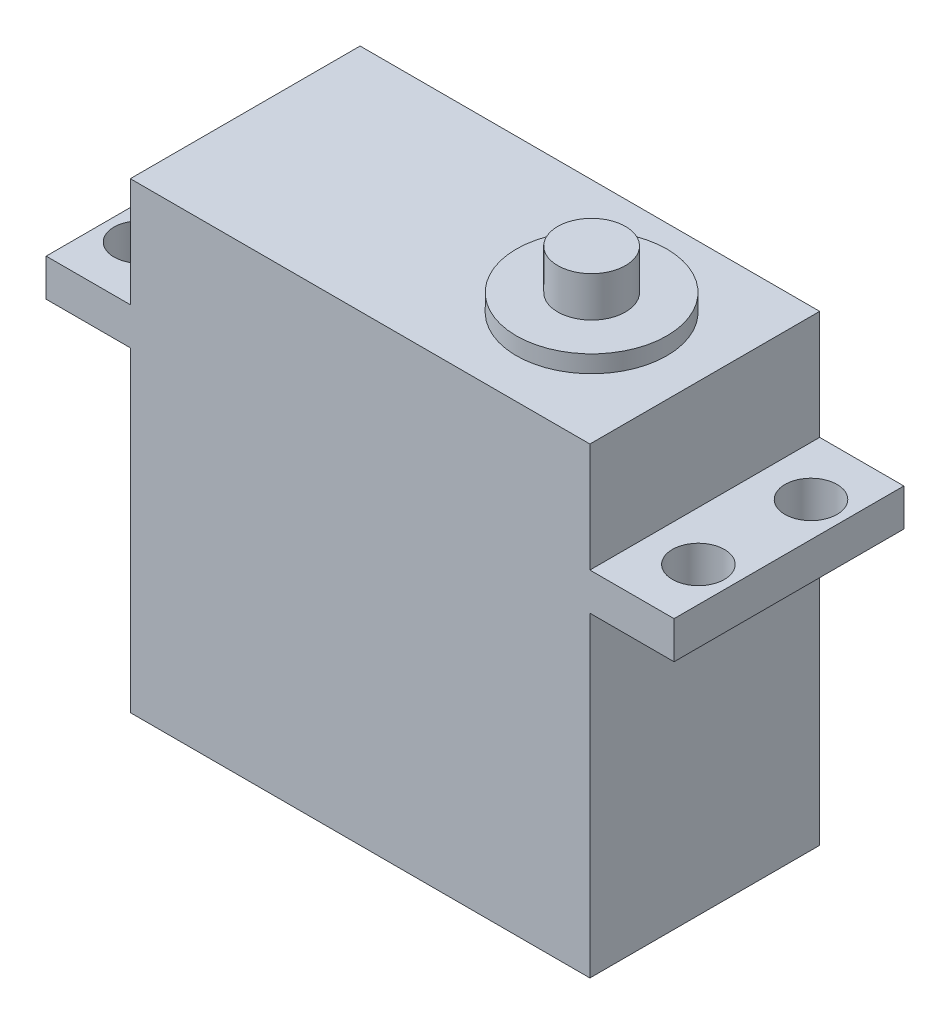
SolidWorks part; units mm, degrees
ref_plane "Front" through (0, 0, 0) normal (0, 0, 1) x (1, 0, 0)
ref_plane "Top" through (0, 0, 0) normal (0, 1, 0) x (1, 0, 0)
ref_plane "Right" through (0, 0, 0) normal (1, 0, 0) x (0, 0, -1)
sketch "Sketch1" plane through (0, 0, 0) normal (0, 0, 1) x (1, 0, 0)
  line L0 (0, 0) -> (40, 0)
  line L1 (40, 0) -> (40, 27.5)
  line L2 (40, 27.5) -> (47.325, 27.5)
  line L3 (47.325, 27.5) -> (47.325, 30.75)
  line L4 (47.325, 30.75) -> (40, 30.75)
  line L5 (40, 30.75) -> (40, 40.25)
  line L6 (40, 40.25) -> (0, 40.25)
  line L7 (0, 40.25) -> (0, 30.75)
  line L8 (0, 30.75) -> (-7.325, 30.75)
  line L9 (-7.325, 30.75) -> (-7.325, 27.5)
  line L10 (-7.325, 27.5) -> (0, 27.5)
  line L11 (0, 27.5) -> (0, 0)
  dimension "D1" = 27.5
  dimension "D2" = 40
  dimension "D3" = 9.5
  dimension "D4" = 54.65
  dimension "D5" = 3.25
extrude "Boss-Extrude1" add sketch "Sketch1" along normal blind 20
sketch "Sketch2" plane through (0, 30.75, 0) normal (0, 1, 0) x (1, 0, 0)
  line L0 (-4.3, -5.0554) -> (20, -5.0554) construction
  line L1 (20, -5.0554) -> (44.3, -5.0554) construction
  line L2 (20, 0) -> (20, -5.0554) construction
  line L3 (40, 0) -> (0, 0) construction
  circle A0 centre (-4.3, -5.0554) radius 2.2648
  circle A1 centre (-4.3, -14.8554) radius 2.2648
  circle A2 centre (44.3, -14.8554) radius 2.2648
  circle A3 centre (44.3, -5.0554) radius 2.2648
  dimension "D1" = 48.6
  dimension "D2" = 9.8
extrude "Cut-Extrude1" cut sketch "Sketch2" against normal up to surface (3.25 mm away) up to face at (-3.6625, 27.5, 10)
sketch "Sketch3" plane through (0, 40.25, 0) normal (0, 1, 0) x (1, 0, 0)
  circle A0 centre (30.15, -10) radius 2.95
  arc A1 (-2.0352, -14.8554) -> (-4.3, -17.1203) centre (-4.3, -14.8554) ccw
  circle A2 centre (-4.3, -14.8554) radius 2.2648 construction
  dimension "D2" = 5.9
  dimension "D1" = 34.45
extrude "Boss-Extrude2" add sketch "Sketch3" along normal blind 5 contours A0 region at (30.15, 40.25, 10)
sketch "Sketch4" plane through (0, 40.25, 0) normal (0, 1, 0) x (1, 0, 0)
  circle A0 centre (30.15, -10) radius 6.55
  dimension "D1" = 13.1
extrude "Boss-Extrude3" add sketch "Sketch4" along normal blind 1.5
ref_axis "Axis1" through (30.15, 45.25, 10) along (0, -1, 0)
